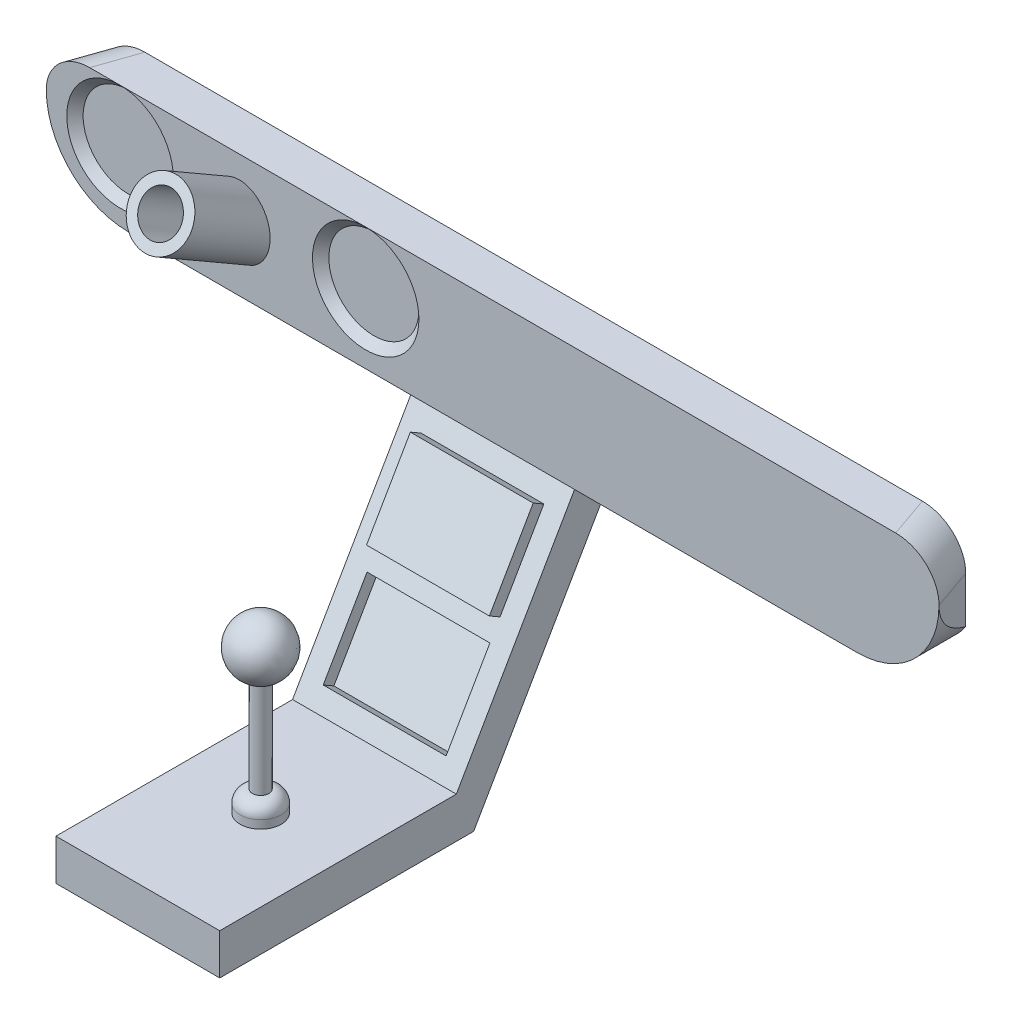
SolidWorks part; units mm, degrees
ref_plane "Front Plane" through (0, 0, 0) normal (0, 0, 1) x (1, 0, 0)
ref_plane "Top Plane" through (0, 0, 0) normal (0, 1, 0) x (1, 0, 0)
ref_plane "Right Plane" through (0, 0, 0) normal (1, 0, 0) x (0, 0, -1)
sketch "Sketch2" plane through (0, 0, 0) normal (0, 0, 1) x (1, 0, 0)
  line L1 (109, -15) -> (-109, -15)
  line L2 (109, -15) -> (109, 15)
  line L3 (109, 15) -> (-109, 15)
  line L4 (-109, -15) -> (-109, 15)
  line L5 (109, -15) -> (-109, 15) construction
  line L6 (109, 15) -> (-109, -15) construction
  point P0 (0, 0)
  dimension "D1" = 218
  dimension "D2" = 30
extrude "Boss-Extrude1" add sketch "Sketch2" along normal mid plane 10
fillet "Fillet1" radius 20 2 edges at (-109, -15, 0) (109, -15, 0)
sketch "Sketch3" plane through (0, 0, 5) normal (0, 0, 1) x (1, 0, 0)
  line L0 (-109, 15) -> (-109, 5) construction
  line L1 (109, 15) -> (-109, 15) construction
  circle A0 centre (-91, 2) radius 10
  circle A1 centre (-31, 2) radius 10
  dimension "D4" = 20
  dimension "D1" = 60
  dimension "D2" = 18
  dimension "D3" = 13
extrude "Cut-Extrude1" cut sketch "Sketch3" against normal mid plane 4
chamfer "Chamfer1" distance 3 angle 45 2 edges at (-21, 2, 5) (-81, 2, 5)
ref_plane "Plane1" through (-61.85, 0, 0) normal (1, 0, 0) x (0, 0, -1)
sketch "Sketch5" plane through (-61.85, 0, 0) normal (1, 0, 0) x (0, 0, -1)
  line L0 (-20.4987, 18.4952) -> (-24.2487, 12)
  line L1 (-20.4987, 18.4952) -> (14.1423, -1.5048)
  line L2 (-24.2487, 12) -> (10.3923, -8)
  line L3 (14.1423, -1.5048) -> (10.3923, -8)
  line L4 (-5, 5) -> (-5, -15) construction
  line L5 (5, -15) -> (-5, -15) construction
  point P0 (0, -2)
  point P3 (0, -2)
  dimension "D1" = 40
  dimension "D2" = 28
  dimension "D3" = 7.5
  dimension "D4" = 120
  dimension "D5" = 13
revolve "Revolve1" add sketch "Sketch5" angle 360 about L2
sketch "Sketch6" plane through (0, 13.5, 23.3827) normal (0, 0.5, 0.866) x (1, 0, 0)
  circle A0 centre (-61.85, -1.7321) radius 5
  dimension "D1" = 10
extrude "Cut-Extrude2" cut sketch "Sketch6" against normal through all
sketch "Sketch7" plane through (0, 0, 0) normal (1, 0, 0) x (0, 0, -1)
  line L0 (5, -15) -> (-5, -15) construction
  line L1 (5, -15) -> (-5, -15)
  line L2 (5, -15) -> (-29.641, -75)
  line L3 (-29.641, -75) -> (-91.641, -75)
  line L4 (-5, 15) -> (5, 15) construction
  line L5 (-5, -15) -> (-33.8675, -65)
  line L6 (-33.8675, -65) -> (-91.641, -65)
  line L7 (-91.641, -65) -> (-91.641, -75)
  dimension "D1" = 90
  dimension "D2" = 120
  dimension "D3" = 62
  dimension "D4" = 10
extrude "Boss-Extrude2" add sketch "Sketch7" along normal mid plane 40
sketch "Sketch8" plane through (0, -1.5849, -2.7452) normal (0, 0.5, 0.866) x (1, 0, 0)
  line L0 (20, -15.4904) -> (-20, -15.4904) construction
  line L1 (-15, -41.8904) -> (15, -41.8904)
  line L2 (-15, -41.8904) -> (-15, -20.4904)
  line L3 (-15, -20.4904) -> (15, -20.4904)
  line L4 (15, -41.8904) -> (15, -20.4904)
  line L5 (-15, -41.8904) -> (15, -20.4904) construction
  line L6 (-15, -20.4904) -> (15, -41.8904) construction
  line L7 (-15, -68.2254) -> (15, -68.2254)
  line L8 (-15, -68.2254) -> (-15, -46.8254)
  line L9 (-15, -46.8254) -> (15, -46.8254)
  line L10 (15, -68.2254) -> (15, -46.8254)
  line L11 (-15, -68.2254) -> (15, -46.8254) construction
  line L12 (-15, -46.8254) -> (15, -68.2254) construction
  line L13 (20, -15.4904) -> (20, -73.2254) construction
  line L14 (-20, -15.4904) -> (-20, -73.2254) construction
  line L15 (20, -73.2254) -> (-20, -73.2254) construction
  point P0 (0, -31.1904)
  point P5 (0, -57.5254)
  dimension "D1" = 5
  dimension "D2" = 5
  dimension "D3" = 5
  dimension "D4" = 21.4
  dimension "D5" = 21.4
  dimension "D6" = 5
  dimension "D7" = 5
  dimension "D8" = 5
extrude "Boss-Extrude4" add sketch "Sketch8" along normal blind 3 contours L1 L4 L3 L2 | L2 L1 L4 L3 region at (0, -28.5966, 12.85)
sketch "Sketch9" plane through (0, -1.5849, -2.7452) normal (0, 0.5, 0.866) x (1, 0, 0)
  line L0 (-20, -15.4904) -> (-20, -73.2254) construction
  line L1 (15, -68.2254) -> (-15, -68.2254)
  line L2 (15, -68.2254) -> (15, -46.8254)
  line L3 (15, -46.8254) -> (-15, -46.8254)
  line L4 (-15, -68.2254) -> (-15, -46.8254)
  line L5 (15, -68.2254) -> (-15, -46.8254) construction
  line L6 (15, -46.8254) -> (-15, -68.2254) construction
  line L7 (20, -15.4904) -> (20, -73.2254) construction
  line L8 (20, -73.2254) -> (-20, -73.2254) construction
  point P0 (0, -57.5254)
  dimension "D1" = 5
  dimension "D2" = 21.4
  dimension "D3" = 5
  dimension "D4" = 5
extrude "Cut-Extrude3" cut sketch "Sketch9" against normal blind 3 contours L4 L1 L2 L3 region at (0, -51.4034, 26.0175)
sketch "Sketch10" plane through (0, 0, 0) normal (1, 0, 0) x (0, 0, -1)
  line L0 (-61.641, -23.0808) -> (-61.641, -85)
  line L1 (-61.641, -85) -> (-54.141, -85)
  line L2 (-54.141, -85) -> (-54.141, -75)
  line L3 (-91.641, -75) -> (-29.641, -75) construction
  line L4 (-54.141, -75) -> (-56.641, -75)
  line L5 (-56.641, -75) -> (-56.641, -63)
  line L6 (-59.641, -60) -> (-59.641, -36.591)
  line L7 (-91.641, -65) -> (-91.641, -75) construction
  line L8 (-33.8675, -65) -> (-91.641, -65) construction
  arc A0 (-56.641, -63) -> (-59.641, -60) centre (-59.641, -63) ccw
  arc A1 (-61.641, -23.0808) -> (-59.641, -36.591) centre (-61.7494, -30) cw
  dimension "D6" = 3
  dimension "D9" = 6.92
  dimension "D1" = 7.5
  dimension "D2" = 30
  dimension "D3" = 10
  dimension "D4" = 5
  dimension "D5" = 2
  dimension "D7" = 2
  dimension "D8" = 35
revolve "Revolve2" add sketch "Sketch10" angle 360 about L0
sketch "Sketch11" plane through (0, 15, 0) normal (0, 1, 0) x (1, 0, 0)
  line L0 (-109, 5) -> (-109, -5)
  line L1 (-109, -5) -> (-105.52, 5)
  line L2 (109, 5) -> (-109, 5) construction
  line L3 (-105.52, 5) -> (-109, 5)
  dimension "D1" = 3.48
extrude "Cut-Extrude4" cut sketch "Sketch11" against normal blind 40
fillet "Fillet2" radius 10 1 edges at (-107.26, 15, 0)
sketch "Sketch13" plane through (0, 15, 0) normal (0, 1, 0) x (1, 0, 0)
  line L0 (109, 5) -> (109, -5)
  line L2 (109, 5) -> (105.52, 5)
  line L3 (109, 5) -> (-94.9318, 5) construction
  line L4 (105.52, 5) -> (109, -5)
  dimension "D1" = 3.48
extrude "Cut-Extrude5" cut sketch "Sketch13" against normal blind 40
fillet "Fillet3" radius 10 1 edges at (107.26, 15, 0)
